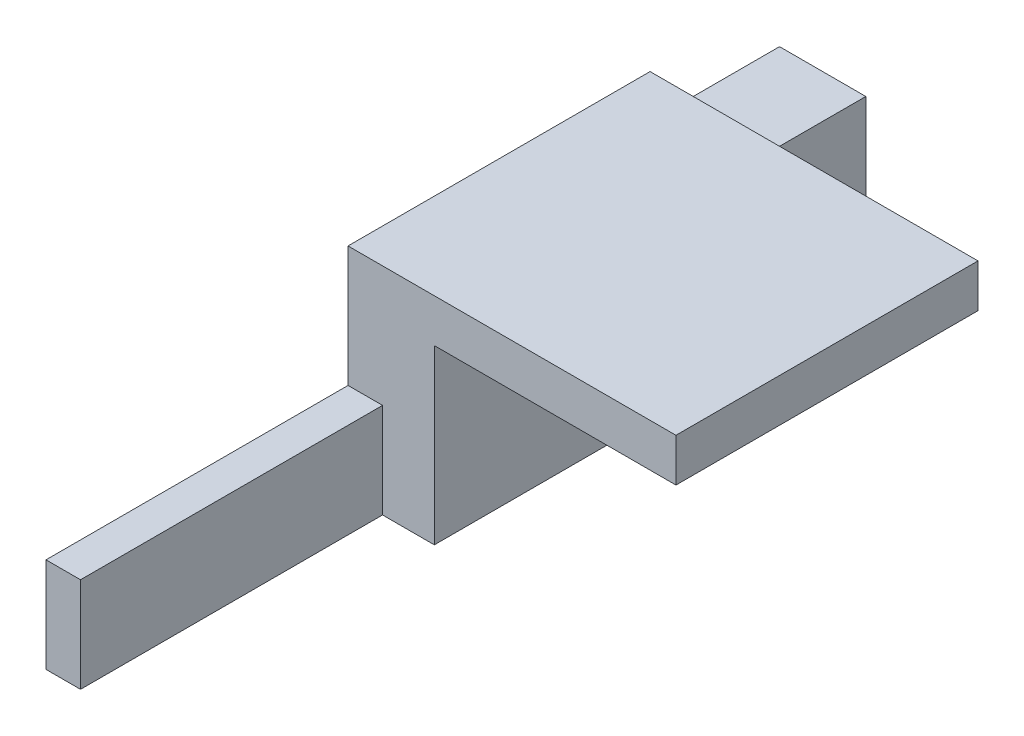
SolidWorks part; units mm, degrees
ref_plane "前视基准面" through (0, 0, 0) normal (0, 0, 1) x (1, 0, 0)
ref_plane "上视基准面" through (0, 0, 0) normal (0, 1, 0) x (1, 0, 0)
ref_plane "右视基准面" through (0, 0, 0) normal (1, 0, 0) x (0, 0, -1)
other "Configuration Table"
sketch "草图1" plane through (0, 0, 0) normal (0, 1, 0) x (1, 0, 0)
  line L5 (38, 0) -> (0, 0)
  line L6 (38, 0) -> (38, -35)
  line L19 (38, -35) -> (0, -35)
  line L20 (0, 0) -> (0, -35)
  line L21 (10, -35) -> (0, -35)
  line L22 (10, -35) -> (10, 15)
  line L23 (10, 15) -> (0, 15)
  line L24 (0, -35) -> (0, 15)
  point P0 (-90.6464, 22.0667)
  dimension "D1" = 35
  dimension "D2" = 38
  dimension "D3" = 10
  dimension "D4" = 50
extrude "凸台-拉伸1" add sketch "草图1" along normal blind 5 contours L5 L20 L19 L6
extrude "凸台-拉伸2" add sketch "草图1<14>" against normal blind 20 contours L23 L24 L21 L22
sketch "草图1<14>" plane through (0, 0, 0) normal (0, 1, 0) x (1, 0, 0) same geometry as "草图1"
sketch "草图2" plane through (10, 0, 0) normal (1, 0, 0) x (0, 0, -1)
  line L0 (-35, 5) -> (-35, -20) construction
  line L1 (-35, -9) -> (-70, -9)
  line L2 (-35, -9) -> (-35, -20)
  line L3 (-35, -20) -> (-70, -20)
  line L4 (-70, -9) -> (-70, -20)
  line L5 (0, 0) -> (15, 0) construction
  line L6 (-35, -20) -> (15, -20) construction
  line L7 (-35, -14.5) -> (-70, -14.5) construction
  circle A1 centre (-67.5, -14.5) radius 0.5
  circle A4 centre (-29.4, -14.5) radius 3.1
  circle A5 centre (-51.7, -14.5) radius 3.1
  point P10 (-70, -14.5)
  point P19 (0, 0)
  dimension "D3" = 1
  dimension "D5" = 6.2
  dimension "D1" = 35
  dimension "D2" = 14.5
  dimension "D4" = 15.8
  dimension "D6" = 22.3
extrude "凸台-拉伸3" add sketch "草图2" along normal blind 4 from surface contours L3 L4 L1 L2 starting at face at (0, -5, 6.6667)
extrude "切除-拉伸1" cut sketch "草图2<3>" along normal blind 3 from surface contours A5 | A4 starting at face at (0, -6, 22.5)
sketch "草图2<3>" plane through (10, 0, 0) normal (1, 0, 0) x (0, 0, -1) same geometry as "草图2"
